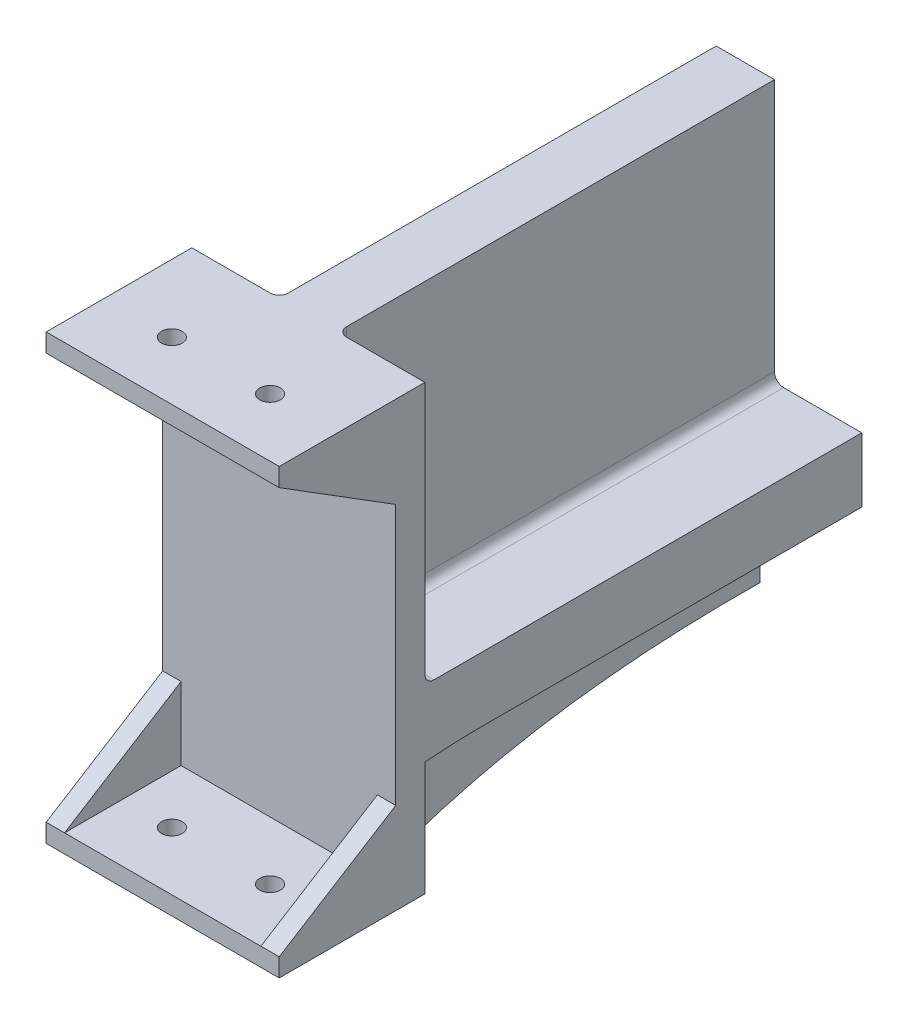
SolidWorks part; units mm, degrees
material "ABS"
ref_plane "X-Y Datum" through (0, 0, 0) normal (0, 0, 1) x (1, 0, 0)
ref_plane "X-Z Datum" through (0, 0, 0) normal (0, 1, 0) x (1, 0, 0)
ref_plane "Y-Z Datum" through (0, 0, 0) normal (1, 0, 0) x (0, 0, -1)
sketch "Sketch1" plane through (0, 0, 0) normal (0, 0, 1) x (1, 0, 0)
  line L1 (-25.4, 48.2854) -> (25.4, 48.2854)
  line L2 (-25.4, 48.2854) -> (-25.4, -48.2854)
  line L3 (-25.4, -48.2854) -> (25.4, -48.2854)
  line L4 (25.4, 48.2854) -> (25.4, -48.2854)
  line L5 (-25.4, 48.2854) -> (25.4, -48.2854) construction
  line L6 (-25.4, -48.2854) -> (25.4, 48.2854) construction
  point P0 (0, 0)
  dimension "D1" = 96.5708
  dimension "D2" = 50.8
extrude "Boss-Extrude1" add sketch "Sketch1" along normal blind 101.6
sketch "Sketch2" plane through (0, -48.2854, 0) normal (0, -1, 0) x (1, 0, 0)
  line L0 (-3.175, 0) -> (3.175, 0)
  line L1 (-25.4, 0) -> (25.4, 0) construction
  line L2 (0, 0) -> (0, 101.6) construction
  line L3 (-25.4, 101.6) -> (25.4, 101.6) construction
  line L4 (-25.4, 95.25) -> (-15.875, 95.25)
  line L5 (-25.4, 101.6) -> (-25.4, 0) construction
  line L6 (25.4, 95.25) -> (15.875, 95.25)
  arc A0 (-15.875, 95.25) -> (-3.175, 0) centre (-333.345, 4.449) cw
  arc A1 (15.875, 95.25) -> (3.175, 0) centre (333.345, 4.449) ccw
  point P5 (0, 0)
  line M5 (-25.4, 0) -> (25.4, 0)
  line M6 (25.4, 0) -> (25.4, 101.6)
  line M8 (-25.4, 101.6) -> (-25.4, 0)
  dimension "D2" = 330.2
  dimension "D1" = 6.35
  dimension "D3" = 6.35
  dimension "D4" = 9.525
extrude "Cut-Extrude1" cut sketch "Sketch2" against normal blind 25.4 and the other way through all contours A0 M8 M5 | A1 M6 M5 region at (15.8837, -48.2854, 42.1228) region at (-15.8837, -48.2854, 42.1228)
fillet "Fillet1" radius 12.7 2 edges at (6.0416, -22.8854, 48.0895) (-6.0416, -22.8854, 48.0895)
fillet "Fillet2" radius 12.7 2 edges at (-15.875, -41.9354, 95.25) (15.875, -41.9354, 95.25)
sketch "Sketch4" plane through (0, 0, 101.6) normal (0, 0, 1) x (1, 0, 0)
  line L0 (25.4, -48.2854) -> (25.4, 48.2854) construction
  line L1 (-25.4, -48.2854) -> (25.4, -48.2854)
  line L2 (-25.4, -48.2854) -> (-25.4, -44.2854)
  line L3 (-25.4, -44.2854) -> (25.4, -44.2854)
  line L4 (25.4, -48.2854) -> (25.4, -44.2854)
  dimension "D1" = 4
extrude "Boss-Extrude2" add sketch "Sketch4" along normal blind 25.4
sketch "Sketch5" plane through (25.4, 0, 0) normal (1, 0, 0) x (0, 0, -1)
  line L0 (-127, -44.2854) -> (-101.6, -28.4104)
  line L1 (-127, -44.2854) -> (-101.6, -44.2854) construction
  line L2 (-101.6, -44.2854) -> (-101.6, 48.2854) construction
  line M7 (-101.6, 48.2854) -> (-101.6, -44.2854)
  line M8 (-101.6, -44.2854) -> (-127, -44.2854)
  dimension "D1" = 15.875
extrude "Boss-Extrude3" add sketch "Sketch5" against normal blind 4 contours L0 M8 M7 region at (25.4, -38.9937, 110.0667)
mirror "Mirror1" about plane through (0, 0, 0) normal (1, 0, 0) of "Boss-Extrude3"
sketch "Sketch6" plane through (0, -44.2854, 0) normal (0, 1, 0) x (1, 0, 0)
  line L0 (21.4, -114.3) -> (-21.4, -114.3) construction
  line L1 (21.4, -127) -> (21.4, -101.6) construction
  line L2 (-21.4, -101.6) -> (-21.4, -127) construction
  line L3 (21.4, -114.3) -> (0, -114.3) construction
  line L4 (0, -114.3) -> (10.7, -114.3) construction
  line L5 (10.7, -114.3) -> (10.7, -129.9826) construction
  line L6 (0, -133.4996) -> (0, -95.1004) construction
  circle A0 centre (10.7, -114.3) radius 2 construction
  circle A1 centre (-10.7, -114.3) radius 2 construction
  point P12 (0, -114.3)
  dimension "D1" = 4
hole_wizard "M4 Clearance Hole1" positions "Sketch7" profile "Sketch8" hole size "M4" standard "ANSI Metric" end condition through all
sketch "Sketch7" plane through (0, -44.2854, 0) normal (0, 1, 0) x (1, 0, 0)
  point P0 (-10.7, -114.3)
  point P3 (10.7, -114.3)
sketch "Sketch8" plane through (-10.7, -44.2854, 114.3) normal (1, 0, 0) x (0, 0, 1)
  line L0 (0, 0) -> (0, 4)
  line L1 (0, 4) -> (2.25, 4)
  line L2 (2.25, 4) -> (2.25, 0)
  line L5 (2.25, 0) -> (0, 0)
  line L11 (0, -6.35) -> (0, 107.95) construction
  dimension "Thru Hole Dia." = 4.5
  dimension "Thru Hole Depth" = 4
mirror "Mirror2" about plane through (0, 0, 0) normal (0, 1, 0) of "M4 Clearance Hole1", "Boss-Extrude3", "Mirror1", "Boss-Extrude2"
sketch "Sketch10" plane through (0, 0, 0) normal (0, 0, -1) x (-1, 0, 0)
  line L0 (-6.35, -8.8646) -> (-6.35, 48.2854)
  line L1 (-25.4, 48.2854) -> (25.4, 48.2854) construction
  line L2 (-6.35, -8.8646) -> (-25.4, -8.8646)
  line L3 (-25.4, -22.8854) -> (-25.4, 48.2854) construction
  line L4 (0, 53.1139) -> (0, -53.1139) construction
  line L5 (6.35, -8.8646) -> (25.4, -8.8646)
  line L6 (6.35, -8.8646) -> (6.35, 48.2854)
  line M10 (25.4, -22.8854) -> (25.4, 48.2854)
  line M11 (25.4, 48.2854) -> (-25.4, 48.2854)
  line M12 (-25.4, 48.2854) -> (-25.4, -22.8854)
  dimension "D1" = 19.05
  dimension "D2" = 57.15
extrude "Cut-Extrude2" cut sketch "Sketch10" against normal blind 95.25 contours L2 L0 M11 M12 | L6 L5 M10 M11 region at (15.875, 19.7104, 0) region at (-15.875, 19.7104, 0)
fillet "Fillet3" radius 2 6 edges at (-15.875, -8.8646, 95.25) (15.875, -8.8646, 95.25) (-6.35, -8.8646, 47.625) (-6.35, 19.7104, 95.25) (6.35, 19.7104, 95.25) (6.35, -8.8646, 47.625)
